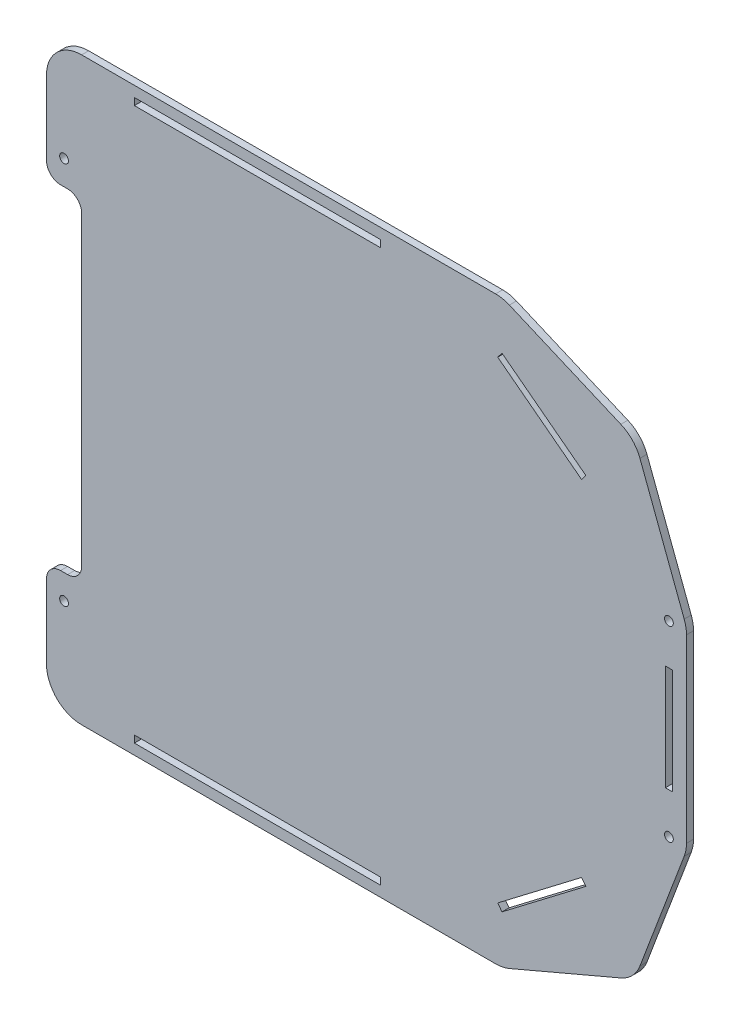
SolidWorks part; units mm, degrees
material "PVC rigido"
ref_plane "Piano frontale" through (0, 0, 0) normal (0, 0, 1) x (1, 0, 0)
ref_plane "Piano superiore" through (0, 0, 0) normal (0, 1, 0) x (1, 0, 0)
ref_plane "Piano destro" through (0, 0, 0) normal (1, 0, 0) x (0, 0, -1)
sketch "Schizzo1" plane through (0, 0, 0) normal (0, 0, 1) x (1, 0, 0)
  line L0 (38.7544, -82.5) -> (76.2532, -66.5077)
  line L1 (-91, -82.5) -> (38.7544, -82.5)
  line L2 (-91, -82.5) -> (-91, 82.5)
  line L3 (-91, 82.5) -> (38.7544, 82.5)
  line L4 (91, -27.5) -> (91, 27.5)
  line L5 (80.4305, -75.7061) -> (42.9317, -91.6984) construction
  line L6 (76.2532, -66.5077) -> (76.2532, 66.5077) construction
  line L7 (76.2532, -66.5077) -> (91, -27.5)
  line L8 (38.7544, 82.5) -> (76.2532, 66.5077)
  line L9 (76.2532, 66.5077) -> (91, 27.5)
  line L10 (38.7544, 82.5) -> (91, 82.5) construction
  line L11 (91, 82.5) -> (91, 27.5) construction
  line L12 (38.7544, -82.5) -> (91, -82.5) construction
  line L13 (91, -82.5) -> (91, -27.5) construction
  line L14 (100.3539, -31.7091) -> (85.8615, -70.0439) construction
  line L15 (85.8615, 70.0439) -> (100.3539, 31.7091) construction
  line L16 (42.9317, 91.6984) -> (80.4305, 75.7061) construction
  line L17 (0, 0) -> (38.7544, 82.5) construction
  line L18 (0, 0) -> (38.7544, -82.5) construction
  line L19 (38.7544, -82.5) -> (38.7544, 82.5) construction
  line L20 (-91, -82.5) -> (0, 0) construction
  line L21 (0, 0) -> (-91, 82.5) construction
  line L22 (0, 0) -> (-91, 0) construction
  line L23 (0, 0) -> (0, 82.5) construction
  line L25 (101, 28.1729) -> (101, -28.1729) construction
  point P0 (0, 0)
  dimension "D1" = 165
  dimension "D2" = 91
  dimension "D3" = 55
  dimension "D4" = 10
extrude "Estrusione-Estrusione1" add sketch "Schizzo1" along normal blind 2
hole_wizard "Foro filettato M3x0.5-1" positions "Schizzo3" profile "Schizzo2" tap size "M3x0.5" standard "Ansi Metric" end condition through all
sketch "Schizzo3" plane through (0, 0, 0) normal (0, 0, -1) x (-1, 0, 0)
  line L0 (86, -82.5) -> (86, -54.5) construction
  line L1 (91, -82.5) -> (-38.7544, -82.5) construction
  line L2 (86, -54.5) -> (86, 54.5) construction
  line L3 (86, 54.5) -> (86, 82.5) construction
  line L4 (-38.7544, 82.5) -> (91, 82.5) construction
  line L6 (0, 0) -> (86, 0) construction
  point P0 (86, -54.5)
  point P2 (86, 54.5)
sketch "Schizzo2" plane through (-86, -54.5, 0) normal (1, 0, 0) x (0, 1, 0)
  line L0 (0, 0) -> (0, 2)
  line L1 (0, 2) -> (1.25, 2)
  line L2 (1.25, 2) -> (1.25, 0)
  line L5 (1.25, 0) -> (0, 0)
  line L11 (0, -6.35) -> (0, 107.95) construction
  dimension "Thru Tap Drill Dia." = 2.5
  dimension "Thru Tap Drill Depth" = 2
cosmetic thread "Filettatura del foro1" parameters "D2"=3
cosmetic thread "Filettatura del foro2" parameters "D2"=3
sketch "Schizzo4" plane through (0, 0, 0) normal (0, 0, -1) x (-1, 0, 0)
  line L0 (31, -77.5) -> (31, 77.5) construction
  line L1 (66, -79.5) -> (-4, -79.5)
  line L2 (66, -79.5) -> (66, -77.5)
  line L3 (66, -77.5) -> (-4, -77.5)
  line L4 (-4, -79.5) -> (-4, -77.5)
  line L5 (66, 77.5) -> (-4, 77.5)
  line L6 (66, 77.5) -> (66, 79.5)
  line L7 (66, 79.5) -> (-4, 79.5)
  line L8 (-4, 77.5) -> (-4, 79.5)
  line L9 (31, 0) -> (91, 0) construction
  line L10 (91, 82.5) -> (91, -82.5) construction
  line L11 (91, -82.5) -> (-38.7544, -82.5) construction
  dimension "D1" = 2
  dimension "D2" = 3
  dimension "D3" = 70
  dimension "D4" = 60
extrude "Taglio-Estrusione1" cut sketch "Schizzo4" against normal blind 10
hole_wizard "Foro filettato M3x0.5-2" positions "Schizzo6" profile "Schizzo5" tap size "M3x0.5" standard "Ansi Metric" end condition through all
sketch "Schizzo6" plane through (0, 0, 2) normal (0, 0, 1) x (1, 0, 0)
  line L16 (71.5763, -64.7396) -> (86, -26.5864)
  line L17 (86, -26.5864) -> (86, 26.5864)
  line L18 (86, 26.5864) -> (71.5763, 64.7396)
  line L19 (71.5763, -64.7396) -> (86, -26.5864) construction
  line L20 (86, -26.5864) -> (86, 26.5864) construction
  line L21 (86, 26.5864) -> (71.5763, 64.7396) construction
  point P0 (86, 26.5864)
  point P2 (86, -26.5864)
  dimension "D1" = 5
sketch "Schizzo5" plane through (86, 26.5864, 2) normal (1, 0, 0) x (0, -1, 0)
  line L0 (0, 0) -> (0, 2)
  line L1 (0, 2) -> (1.25, 2)
  line L2 (1.25, 2) -> (1.25, 0)
  line L5 (1.25, 0) -> (0, 0)
  line L11 (0, -6.35) -> (0, 107.95) construction
  dimension "Thru Tap Drill Dia." = 2.5
  dimension "Thru Tap Drill Depth" = 2
cosmetic thread "Filettatura del foro3" parameters "D2"=3
cosmetic thread "Filettatura del foro4" parameters "D2"=3
sketch "Schizzo7" plane through (0, 0, 2) normal (0, 0, 1) x (1, 0, 0)
  line L0 (38.5362, 68.798) -> (62.3843, 50.5973)
  line L1 (61.1709, 49.0074) -> (37.3228, 67.2081)
  line L2 (37.3228, 67.2081) -> (38.5362, 68.798)
  line L3 (61.1709, 49.0074) -> (62.3843, 50.5973)
  line L4 (86, 26.5864) -> (4, 78.5) construction
  line L5 (4, 79.5) -> (4, 77.5) construction
  line L6 (4, 79.5) -> (4, 77.5) construction
  line L7 (37.9295, 68.0031) -> (61.7776, 49.8023) construction
  line L8 (49.8535, 58.9027) -> (45, 52.5432) construction
  line L9 (86, 26.5864) -> (86, 15) construction
  line L10 (86, 15) -> (86, -15) construction
  line L11 (86, -15) -> (86, -26.5864) construction
  line L12 (86, -26.5864) -> (4, -78.5) construction
  line L13 (76.2532, -66.5077) -> (49.8535, -58.9027) construction
  line L14 (61.7776, -49.8023) -> (91, -27.5) construction
  line L15 (4, -77.5) -> (4, -79.5) construction
  line L16 (61.1709, -49.0074) -> (37.3228, -67.2081)
  line L17 (37.3228, -67.2081) -> (38.5362, -68.798)
  line L18 (38.5362, -68.798) -> (62.3843, -50.5973)
  line L19 (62.3843, -50.5973) -> (61.1709, -49.0074)
  line L20 (61.7776, -49.8023) -> (37.9295, -68.0031) construction
  line L21 (45, -52.5432) -> (49.8535, -58.9027) construction
  line L22 (91, 27.5) -> (61.7776, 49.8023) construction
  line L23 (87, -15) -> (85, -15)
  line L24 (87, -15) -> (87, 15)
  line L25 (87, 15) -> (85, 15)
  line L26 (85, -15) -> (85, 15)
  dimension "D1" = 30
  dimension "D2" = 8
  dimension "D3" = 30
extrude "Taglio-Estrusione2" cut sketch "Schizzo7" against normal blind 10
sketch "Schizzo8" plane through (0, 0, 2) normal (0, 0, 1) x (1, 0, 0)
  line L0 (-91, 82.5) -> (-91, -82.5) construction
  line L1 (-91, -47.5) -> (-81, -47.5)
  line L2 (-91, -47.5) -> (-91, 47.5)
  line L3 (-91, 47.5) -> (-81, 47.5)
  line L4 (-81, -47.5) -> (-81, 47.5)
  line L5 (-86, -54.5) -> (-86, -47.5) construction
  line L6 (-86, 54.5) -> (-86, 47.5) construction
  dimension "D1" = 95
extrude "Taglio-Estrusione3" cut sketch "Schizzo8" against normal blind 10
fillet "Raccordo1" radius 10 2 edges at (-91, 82.5, 1) (-91, -82.5, 1)
fillet "Raccordo2" radius 10 6 edges at (38.7544, -82.5, 1) (76.2532, -66.5077, 1) (91, -27.5, 1) (91, 27.5, 1) (76.2532, 66.5077, 1) (38.7544, 82.5, 1)
fillet "Raccordo3" radius 4 4 edges at (-81, 47.5, 1) (-91, 47.5, 1) (-81, -47.5, 1) (-91, -47.5, 1)
sketch "Schizzo9" plane through (0, 0, 2) normal (0, 0, 1) x (1, 0, 0)
  line L0 (-2.0763, 31.6435) -> (-2.0763, -8.3551)
  line L1 (-22.0756, 11.6442) -> (17.923, 11.6442)
  line L2 (-2.0763, 11.6442) -> (-2.7758, 15.5826) construction
  line L3 (-2.7758, 15.5826) -> (-4.1747, 23.4586) construction
  line L4 (-4.1747, 23.4586) -> (-5.5735, 31.3347) construction
  line L5 (-15.0728, -3.5566) -> (10.9201, 26.845)
  line L6 (10.2297, -4.1208) -> (-14.3823, 27.4092)
  circle A0 centre (-2.0763, 11.6442) radius 19.9993
  circle A1 centre (-2.0763, 11.6442) radius 11.9993
  circle A2 centre (-2.0763, 11.6442) radius 4
  point P9 (-2.0763, 11.6442)
  dimension "D1" = 8
  dimension "D2" = 8
other "Ventola1" [suppressed] parameters "RibsDepth"=1, "RibsWidth"=5, "RibsOffset"=0, "SparsDepth"=1, "SparsWidth"=2, "SparsOffset"=0, "SupportDepth"=1, "SupportOffset"=0, "Draft"=1
